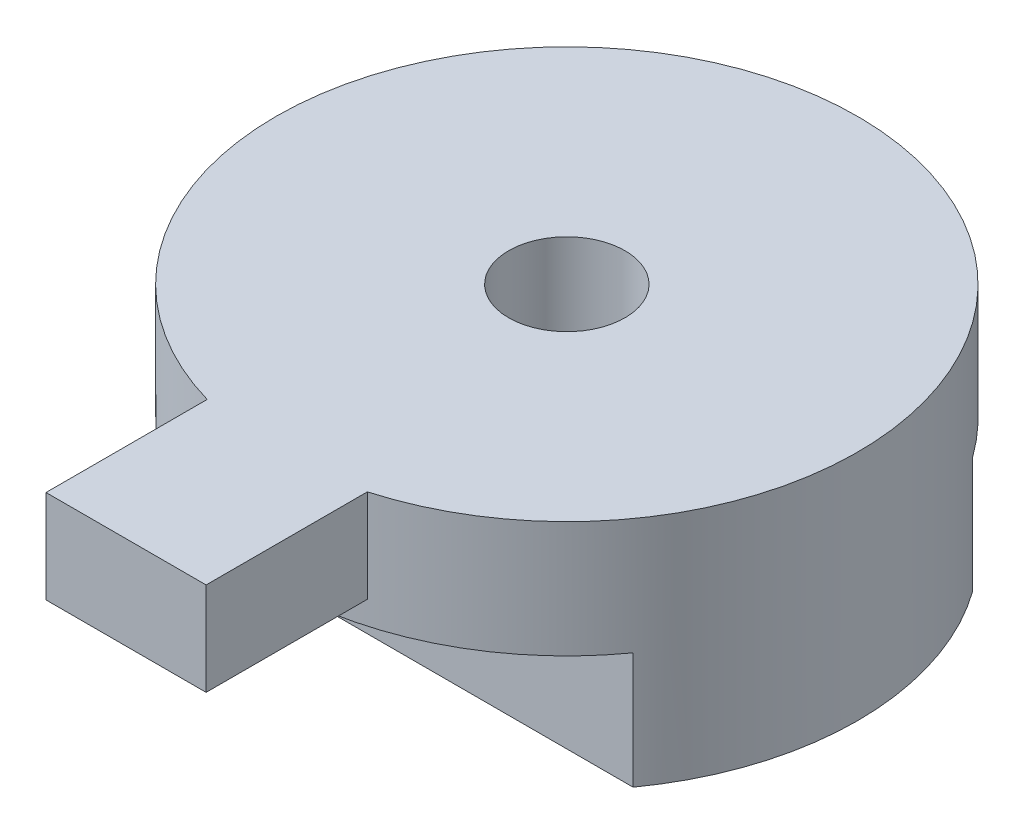
SolidWorks part; units mm, degrees
ref_plane "Front Plane" through (0, 0, 0) normal (0, 0, 1) x (1, 0, 0)
ref_plane "Top Plane" through (0, 0, 0) normal (0, 1, 0) x (1, 0, 0)
ref_plane "Right Plane" through (0, 0, 0) normal (1, 0, 0) x (0, 0, -1)
sketch "Sketch1" plane through (0, 0, 0) normal (0, 1, 0) x (1, 0, 0)
  circle A0 centre (0, 0) radius 15.875
  dimension "D1" = 31.75
extrude "Boss-Extrude1" add sketch "Sketch1" along normal blind 12.7
sketch "Sketch2" plane through (0, 0, 0) normal (1, 0, 0) x (0, 0, -1)
  line L0 (0, 0) -> (0, 50000) construction
  line L1 (-15.875, 0) -> (15.875, 0) construction
  line L2 (15.875, 0) -> (9.271, 0)
  line L3 (-15.875, 0) -> (-9.271, 0)
  line L4 (-15.875, 0) -> (-15.875, 6.35)
  line L5 (-15.875, 6.35) -> (-9.271, 6.35)
  line L6 (-9.271, 0) -> (-9.271, 6.35)
  line L7 (9.271, 0) -> (9.271, 6.35)
  line L8 (15.875, 0) -> (15.875, 6.35)
  line L9 (15.875, 6.35) -> (9.271, 6.35)
  point P4 (0, 0)
  dimension "D1" = 18.542
  dimension "D2" = 6.35
extrude "Cut-Extrude1" cut sketch "Sketch2" against normal through all and the other way through all
sketch "Sketch3" plane through (0, 12.7, 0) normal (0, 1, 0) x (1, 0, 0)
  circle A0 centre (0, 0) radius 3.175
  dimension "D1" = 6.35
extrude "Cut-Extrude2" cut sketch "Sketch3" against normal blind 12.7
sketch "Sketch4" plane through (0, 12.7, 0) normal (0, 1, 0) x (1, 0, 0)
  line L1 (-4.3704, -7.6879) -> (4.3704, -7.6879)
  line L2 (-4.3704, -7.6879) -> (-4.3704, -24.0621)
  line L3 (-4.3704, -24.0621) -> (4.3704, -24.0621)
  line L4 (4.3704, -7.6879) -> (4.3704, -24.0621)
  line L5 (-4.3704, -7.6879) -> (4.3704, -24.0621) construction
  line L6 (-4.3704, -24.0621) -> (4.3704, -7.6879) construction
  arc A0 (-12.8866, -9.271) -> (12.8866, -9.271) centre (0, 0) ccw construction
  point P0 (0, -15.875)
  point P8 (4.3704, -24.0621)
extrude "Boss-Extrude2" add sketch "Sketch4" against normal blind 5.08
